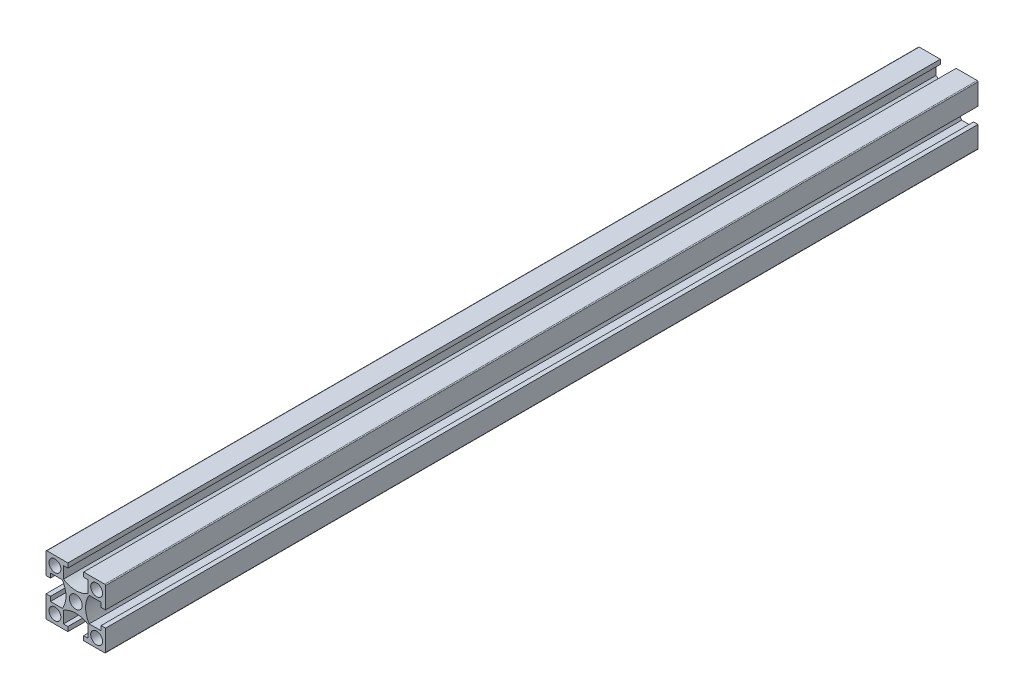
SolidWorks part; units mm, degrees
ref_plane "정면" through (0, 0, 0) normal (0, 0, 1) x (1, 0, 0)
ref_plane "윗면" through (0, 0, 0) normal (0, 1, 0) x (1, 0, 0)
ref_plane "우측면" through (0, 0, 0) normal (1, 0, 0) x (0, 0, -1)
sketch "스케치1" plane through (0, 0, 0) normal (0, 0, 1) x (1, 0, 0)
  line L0 (0, 32.0265) -> (0, -31.6588) construction
  line L1 (-10, 10) -> (-10, -10)
  line L2 (-10, 10) -> (10, 10)
  line L3 (-10, 2.65) -> (-8.5, 2.65)
  line L4 (13.6618, 0) -> (-11.6993, 0) construction
  line L5 (-8.5, 2.65) -> (-8.5, 4.15)
  line L6 (-8.5, 4.15) -> (-4.5032, 4.15)
  line L7 (-10, -2.65) -> (-8.5, -2.65)
  line L8 (-8.5, -2.65) -> (-8.5, -4.15)
  line L9 (-8.5, -4.15) -> (-4.5032, -4.15)
  line L10 (-10, -10) -> (10, -10)
  line L11 (10, 10) -> (10, -10)
  circle A0 centre (-7, 7) radius 2
  circle A1 centre (-7, -7) radius 2
  arc A2 (-4.5032, 4.15) -> (-4.5032, -4.15) centre (-11.0587, 0) cw
  circle A3 centre (0, 0) radius 2.15
  circle A4 centre (7, 7) radius 2
  circle A5 centre (7, -7) radius 2
  point P21 (-10, 0)
  point P23 (-3.3, 0)
  point P31 (0, -10)
  point P32 (0, 10)
  dimension "D3" = 4
  dimension "D9" = 6.7
  dimension "D10" = 4.3
  dimension "D11" = 7.7587
  dimension "D1" = 20
  dimension "D2" = 20
  dimension "D4" = 14
  dimension "D5" = 14
  dimension "D6" = 5.3
  dimension "D7" = 8.3
  dimension "D8" = 1.5
extrude "보스-돌출1" add sketch "스케치1" along normal blind 293 contours A0 | A4 | A3 | A5 | A1 | A2 L6 L5 L3 L1 L7 L8 L9 | L2 L11 L10 L1 region at (-6.6069, 0, 0) region at (-7, 7, 0) region at (-7, -7, 0) region at (0, 0, 0) region at (7, 7, 0) region at (7, -7, 0)
extrude "컷-돌출1" cut sketch "스케치1<3>" along normal up to next contours A2 L6 L5 L3 L1 L7 L8 L9 region at (-6.6069, 0, 0)
sketch "스케치1<3>" plane through (0, 0, 0) normal (0, 0, 1) x (1, 0, 0) same geometry as "스케치1"
pattern_circular "원형 패턴1" count 4 over 360 about axis through (0, 0, 293) along (0, 0, -1) of "컷-돌출1" reverse direction yes
fillet "필렛1" radius 0.3 4 edges at (10, -10, 146.5) (-10, -10, 146.5) (-10, 10, 146.5) (10, 10, 146.5)
sketch "스케치2" plane through (0, 0, 0) normal (1, 0, 0) x (0, 0, -1)
  circle A0 centre (-25, 0) radius 2.5
  dimension "D1" = 5
  dimension "D2" = 25
extrude "컷-돌출2" cut sketch "스케치2" against normal through all both and the other way through all
